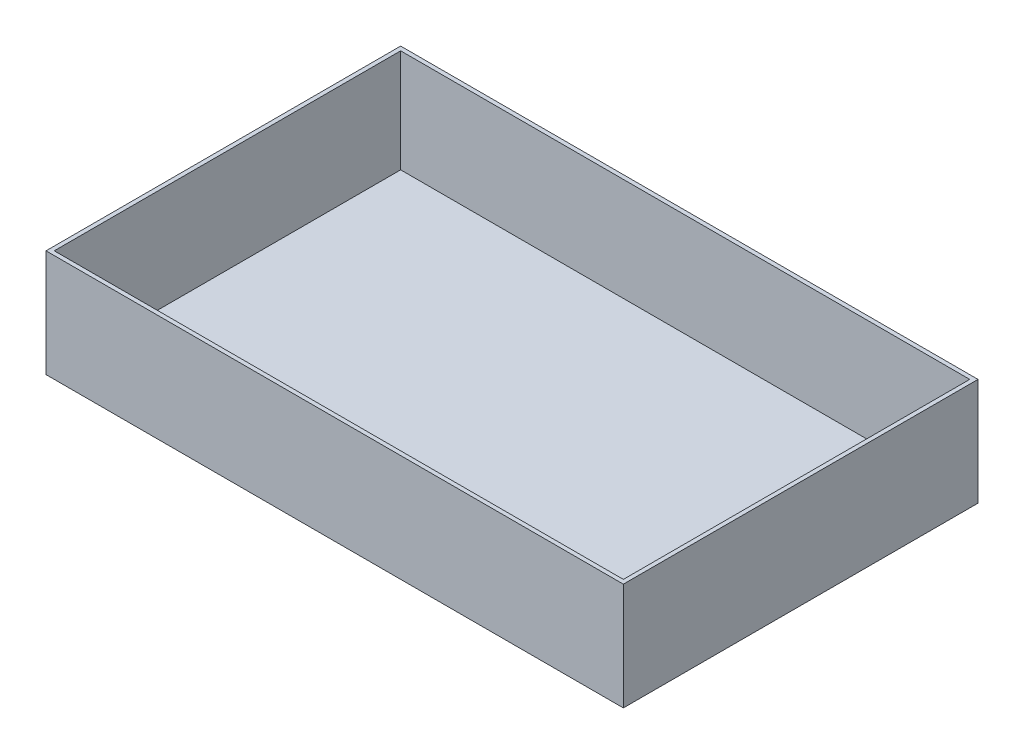
SolidWorks part; units mm, degrees
ref_plane "Front Plane" through (0, 0, 0) normal (0, 0, 1) x (1, 0, 0)
ref_plane "Top Plane" through (0, 0, 0) normal (0, 1, 0) x (1, 0, 0)
ref_plane "Right Plane" through (0, 0, 0) normal (1, 0, 0) x (0, 0, -1)
sketch "Sketch1" plane through (0, 0, 0) normal (0, 1, 0) x (1, 0, 0)
  line L1 (-350, 215) -> (350, 215)
  line L2 (-350, 215) -> (-350, -215)
  line L3 (-350, -215) -> (350, -215)
  line L4 (350, 215) -> (350, -215)
  line L5 (-350, 215) -> (350, -215) construction
  line L6 (-350, -215) -> (350, 215) construction
  point P0 (0, 0)
  dimension "D1" = 700
  dimension "D2" = 430
extrude "Boss-Extrude1" add sketch "Sketch1" along normal blind 130
shell "Shell2" thickness 5 removed face at (0, 130, 0)
